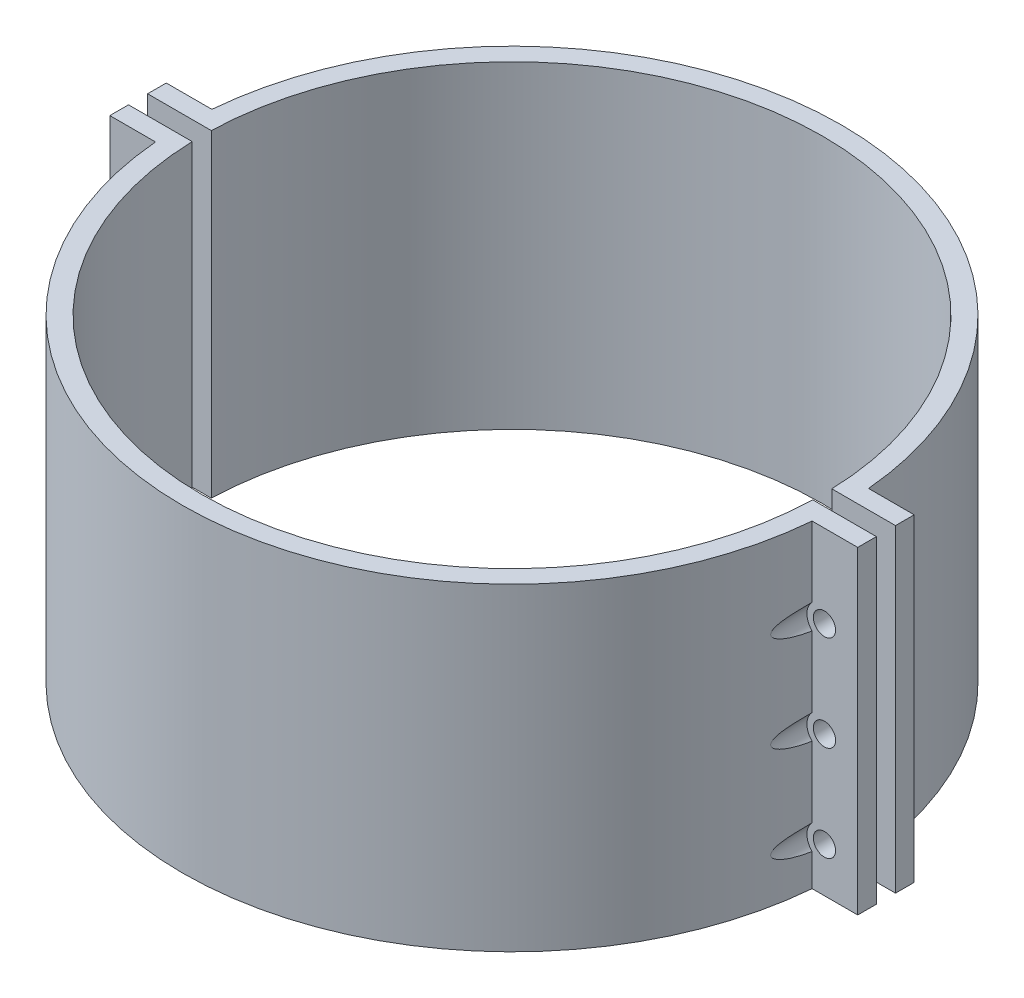
SolidWorks part; units mm, degrees
ref_plane "Front Plane" through (0, 0, 0) normal (0, 0, 1) x (1, 0, 0)
ref_plane "Top Plane" through (0, 0, 0) normal (0, 1, 0) x (1, 0, 0)
ref_plane "Right Plane" through (0, 0, 0) normal (1, 0, 0) x (0, 0, -1)
sketch "Sketch1" plane through (0, 0, 0) normal (0, 1, 0) x (1, 0, 0)
  line L0 (-68.1891, 0) -> (51.75, 0) construction
  line L1 (-58.7269, -1.5) -> (-48.7269, -1.5)
  line L2 (-58.7269, 1.5) -> (-48.7269, 1.5)
  line L3 (-58.7269, -1.5) -> (-58.7269, -4.432)
  line L4 (-58.7269, -4.432) -> (-51.5599, -4.432)
  line L5 (-58.7269, 1.5) -> (-58.7269, 4.432)
  line L6 (-58.7269, 4.432) -> (-51.5599, 4.432)
  line L7 (0, -59.7416) -> (0, 60.0429) construction
  line L8 (58.7269, -1.5) -> (48.7269, -1.5)
  line L9 (58.7269, -4.432) -> (51.5599, -4.432)
  line L10 (58.7269, -1.5) -> (58.7269, -4.432)
  line L11 (58.7269, 1.5) -> (48.7269, 1.5)
  line L12 (58.7269, 1.5) -> (58.7269, 4.432)
  line L13 (58.7269, 4.432) -> (51.5599, 4.432)
  arc A0 (-48.7269, -1.5) -> (48.7269, -1.5) centre (0, 0) ccw
  arc A1 (-51.75, 0) -> (-51.7283, -1.5) centre (0, 0) ccw
  circle A2 centre (0, 0) radius 51.75 construction
  circle A3 centre (0, 0) radius 48.75 construction
  arc A4 (-51.5599, -4.432) -> (51.5599, -4.432) centre (0, 0) ccw
  arc A5 (48.7269, 1.5) -> (-48.7269, 1.5) centre (0, 0) ccw
  arc A6 (51.5599, 4.432) -> (-51.5599, 4.432) centre (0, 0) ccw
  dimension "D1" = 97.5
  dimension "D3" = 3
  dimension "D4" = 10
  dimension "D2" = 3
extrude "Boss-Extrude1" add sketch "Sketch1" along normal blind 50 contours L4 A4 L9 L10 L8 A0 L1 L3 | A6 L6 L5 L2 A5 L11 L12 L13 region at (-55.2276, 0, 2.7775)
sketch "Sketch2" plane through (0, 0, 4.432) normal (0, 0, 1) x (1, 0, 0)
  line L0 (0, 57.4382) -> (0, -5.5464) construction
  line L1 (-53.5, 59.7194) -> (-53.5, -8.2171) construction
  line L2 (-58.7269, 0) -> (-51.5599, 0) construction
  circle A0 centre (-53.5, 7) radius 1.75
  circle A1 centre (-53.5, 22) radius 1.75
  circle A2 centre (-53.5, 37) radius 1.75
  circle A3 centre (53.5, 7) radius 1.75
  circle A4 centre (53.5, 22) radius 1.75
  circle A5 centre (53.5, 37) radius 1.75
  dimension "D5" = 3.5
  dimension "D6" = 3.5
  dimension "D7" = 3.5
  dimension "D1" = 53.5
  dimension "D2" = 7
  dimension "D3" = 15
  dimension "D4" = 15
extrude "Cut-Extrude1" cut sketch "Sketch2" against normal through all
sketch "Sketch3" plane through (0, 0, 4.432) normal (0, 0, 1) x (1, 0, 0)
  line L0 (0, 54.5816) -> (0, -6.8451) construction
  circle A0 centre (-53.5, 37) radius 2.75
  circle A1 centre (-53.5, 22) radius 2.75
  circle A2 centre (-53.5, 7) radius 2.75
  circle A3 centre (53.5, 7) radius 2.75
  circle A4 centre (53.5, 22) radius 2.75
  circle A5 centre (53.5, 37) radius 2.75
  circle A6 centre (53.5, 7) radius 1.75 construction
  circle A7 centre (53.5, 22) radius 1.75 construction
  circle A8 centre (53.5, 37) radius 1.75 construction
  circle A9 centre (-53.5, 7) radius 1.75 construction
  circle A10 centre (-53.5, 22) radius 1.75 construction
  circle A11 centre (-53.5, 37) radius 1.75 construction
  circle A12 centre (53.5, 7) radius 1.75
  circle A13 centre (53.5, 22) radius 1.75
  circle A14 centre (53.5, 37) radius 1.75
  circle A15 centre (-53.5, 7) radius 1.75
  circle A16 centre (-53.5, 22) radius 1.75
  circle A17 centre (-53.5, 37) radius 1.75
  dimension "D2" = 5.5
  dimension "D3" = 5.5
  dimension "D4" = 5.5
extrude "Cut-Extrude3" cut sketch "Sketch3" along normal blind 50
ref_plane "Plane1" through (0, 0, 0) normal (0, 0, 1) x (0, -1, 0)
sketch "Sketch5" plane through (0, 0, -4.432) normal (0, 0, -1) x (-1, 0, 0)
  line L0 (0, 54.4273) -> (0, -7.504) construction
  line L1 (0, 50) -> (0, 0) construction
  circle A0 centre (53.5, 7) radius 1.75 construction
  circle A1 centre (53.5, 22) radius 1.75 construction
  circle A2 centre (53.5, 37) radius 1.75 construction
  circle A3 centre (-53.5, 7) radius 1.75 construction
  circle A4 centre (-53.5, 22) radius 1.75 construction
  circle A5 centre (-53.5, 37) radius 1.75 construction
  circle A6 centre (53.5, 7) radius 1.75
  circle A7 centre (53.5, 22) radius 1.75
  circle A8 centre (53.5, 37) radius 1.75
  circle A9 centre (-53.5, 7) radius 1.75
  circle A10 centre (-53.5, 22) radius 1.75
  circle A11 centre (-53.5, 37) radius 1.75
  circle A12 centre (-53.5, 37) radius 2.75
  circle A13 centre (-53.5, 22) radius 2.75
  circle A14 centre (-53.5, 7) radius 2.75
  circle A15 centre (53.5, 7) radius 2.75
  circle A16 centre (53.5, 22) radius 2.75
  circle A17 centre (53.5, 37) radius 2.75
  dimension "D1" = 5.5
  dimension "D2" = 5.5
  dimension "D3" = 5.5
extrude "Cut-Extrude4" cut sketch "Sketch5" along normal blind 50
